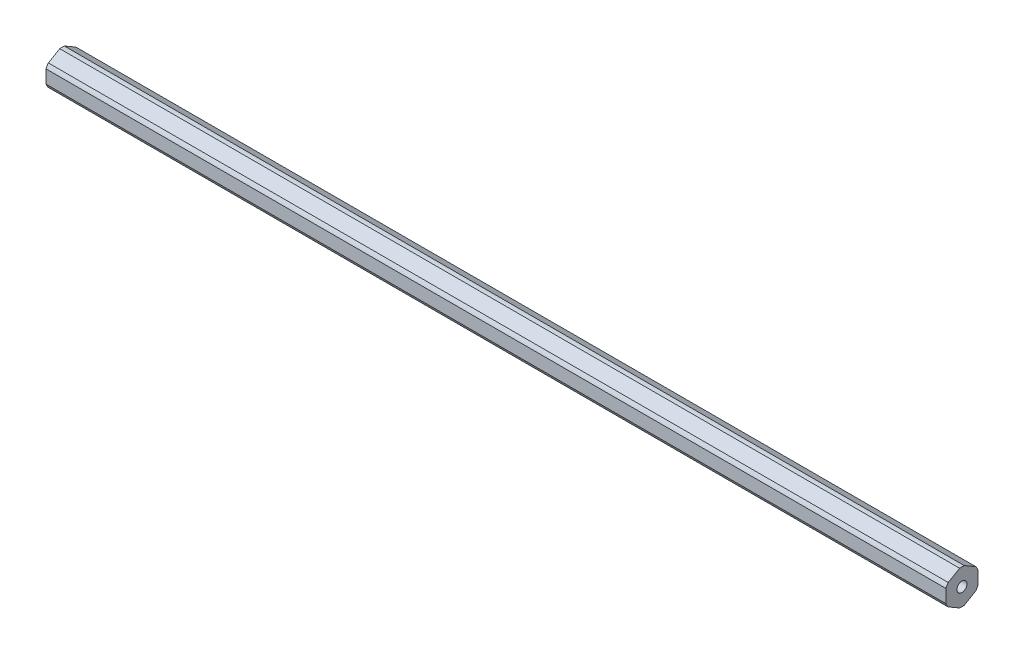
SolidWorks part; units mm, degrees
material "6061 Alloy"
ref_plane "Front Plane" through (0, 0, 0) normal (0, 0, 1) x (1, 0, 0)
ref_plane "Top Plane" through (0, 0, 0) normal (0, 1, 0) x (1, 0, 0)
ref_plane "Right Plane" through (0, 0, 0) normal (1, 0, 0) x (0, 0, -1)
ref_plane "Plane1" through (914.4, 0, 0) normal (1, 0, 0) x (0, 0, -1)
sketch "Sketch1" plane through (914.4, 0, 0) normal (1, 0, 0) x (0, 0, -1)
  line L0 (-5.4343, -4.1949) -> (-0.9157, -6.8037)
  line L1 (0.9157, -6.8037) -> (5.4343, -4.1949)
  line L2 (6.35, -2.6088) -> (6.35, 2.6088)
  line L3 (5.4343, 4.1949) -> (0.9157, 6.8037)
  line L4 (-0.9157, 6.8037) -> (-5.4343, 4.1949)
  line L5 (-6.35, 2.6088) -> (-6.35, -2.6088)
  circle A0 centre (0, 0) radius 1.9939
  arc A1 (-6.35, -2.6088) -> (-5.4343, -4.1949) centre (0, 0) ccw
  arc A2 (-0.9157, -6.8037) -> (0.9157, -6.8037) centre (0, 0) ccw
  arc A3 (5.4343, -4.1949) -> (6.35, -2.6088) centre (0, 0) ccw
  arc A4 (6.35, 2.6088) -> (5.4343, 4.1949) centre (0, 0) ccw
  arc A5 (0.9157, 6.8037) -> (-0.9157, 6.8037) centre (0, 0) ccw
  arc A6 (-5.4343, 4.1949) -> (-6.35, 2.6088) centre (0, 0) ccw
extrude "Boss-Extrude1" add sketch "Sketch1" against normal blind 355.6
equation "\"Hex Length\"= 14in"
equation "\"D1@Boss-Extrude1\"=\"Hex Length\""
